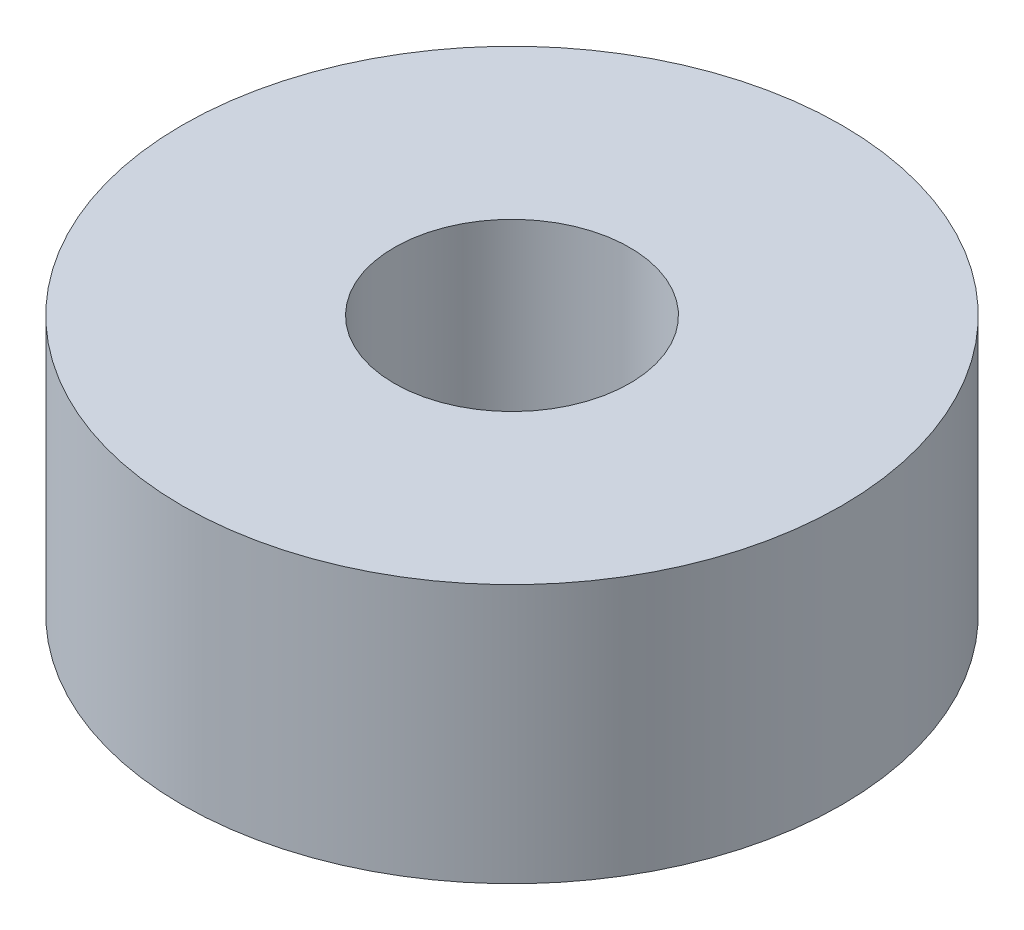
SolidWorks part; units mm, degrees
ref_plane "Front Plane" through (0, 0, 0) normal (0, 0, 1) x (1, 0, 0)
ref_plane "Top Plane" through (0, 0, 0) normal (0, 1, 0) x (1, 0, 0)
ref_plane "Right Plane" through (0, 0, 0) normal (1, 0, 0) x (0, 0, -1)
ref_axis "Axis1" through (0, -55, 0) along (0, 1, 0)
sketch "Sketch1" plane through (0, 0, 0) normal (0, 1, 0) x (1, 0, 0)
  circle A0 centre (0, 0) radius 3.9688
  circle A1 centre (0, 0) radius 11.1125
  dimension "D1" = 7.9375
  dimension "D2" = 22.225
extrude "Boss-Extrude1" add sketch "Sketch1" along normal blind 8.7312
